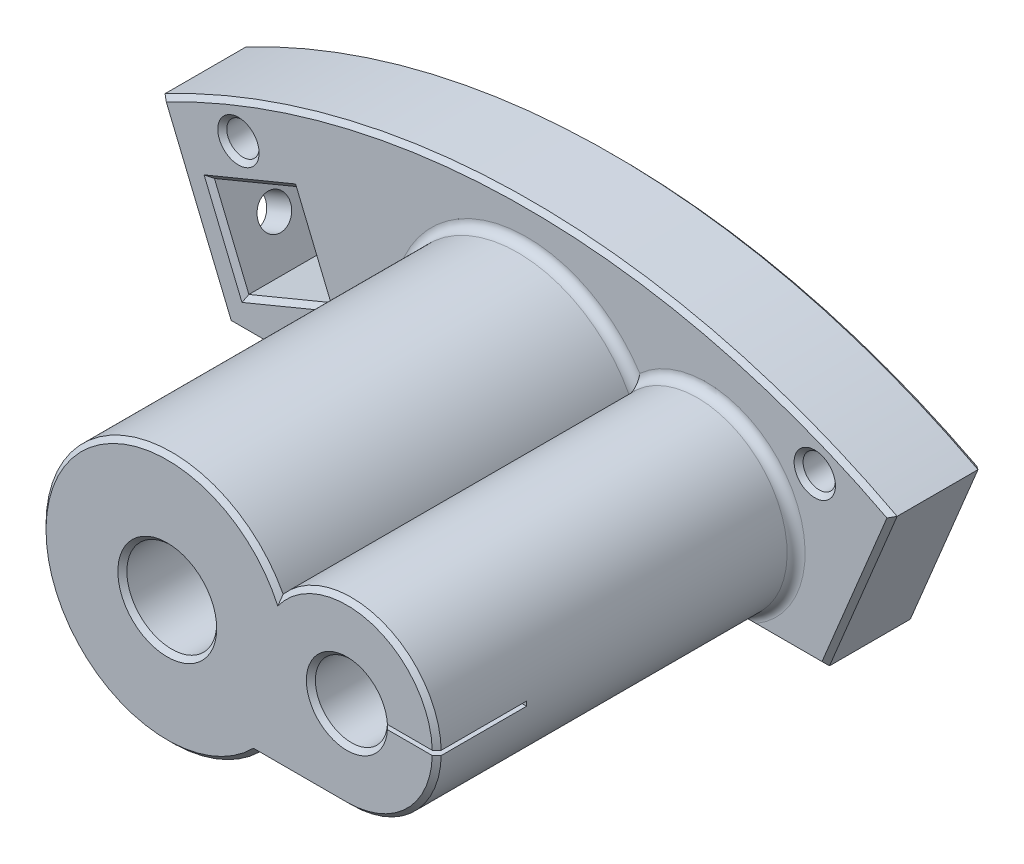
SolidWorks part; units mm, degrees
ref_plane "Front Plane" through (0, 0, 0) normal (0, 0, 1) x (1, 0, 0)
ref_plane "Top Plane" through (0, 0, 0) normal (0, 1, 0) x (1, 0, 0)
ref_plane "Right Plane" through (0, 0, 0) normal (1, 0, 0) x (0, 0, -1)
sketch "Sketch1" plane through (0, 0, 0) normal (0, 0, 1) x (1, 0, 0)
  line L0 (-46.9014, 0) -> (43.5211, 0) construction
  line L1 (0, 38.5211) -> (0, -80.4339) construction
  line L2 (-33.5349, -69.25) -> (36.7559, -69.25) construction
  line L3 (0, -69.25) -> (-37.9703, 22.4183) construction
  line L4 (-40.7467, 8.1836) -> (-33.2148, -10)
  line L5 (-25.9885, 6.5901) -> (-35.2504, 2.7537)
  line L6 (-35.2504, 2.7537) -> (-31.414, -6.5082)
  line L7 (-31.414, -6.5082) -> (-22.1521, -2.6718)
  line L8 (-22.1521, -2.6718) -> (-25.9885, 6.5901)
  line L9 (-33.2148, -10) -> (-9.798, -10)
  line L10 (33.2148, -10) -> (9.798, -10)
  line L11 (40.7467, 8.1836) -> (33.2148, -10)
  line L12 (20, 7.6656) -> (20, -13.8845) construction
  circle A1 centre (-28.7013, 0.041) radius 5.0125 construction
  arc A2 (40.7467, 8.1836) -> (-40.7467, 8.1836) centre (0, -69.25) ccw
  arc A5 (-9.798, -10) -> (9.798, -10) centre (0, 0) ccw
  circle A6 centre (0, 0) radius 5
  circle A7 centre (-32.0765, 8.1894) radius 1.8
  circle A8 centre (32.0765, 8.1894) radius 1.8
  circle A9 centre (20, 0) radius 3
  point P32 (0, -14)
  dimension "D2" = 20
  dimension "D7" = 75
  dimension "D8" = 175
  dimension "D9" = 3
  dimension "D10" = 14
  dimension "D12" = 10
  dimension "D13" = 3.6
  dimension "D14" = 32.0765
  dimension "D16" = 6
  dimension "D3" = 69.25
  dimension "D4" = 22.5
  dimension "D5" = 10.025
  dimension "D6" = 90
  dimension "D11" = 10
extrude "Boss-Extrude1" add sketch "Sketch1" along normal blind 10
sketch "Sketch3" plane through (0, 0, 0) normal (0, 0, -1) x (-1, 0, 0)
  circle A0 centre (0, 0) radius 11.025
  dimension "D1" = 22.05
sketch "Sketch4" plane through (0, 0, 0) normal (0, 0, -1) x (-1, 0, 0)
  circle A0 centre (0, 0) radius 12.525
  dimension "D1" = 25.05
sketch "Sketch5" plane through (-29.1145, -12.0596, 0) normal (0.9239, 0.3827, 0) x (0, 0, -1)
  line L5 (-10, 16.0338) -> (0, 16.0338) construction
  line L6 (0, 16.0338) -> (0, 6.0088) construction
  circle A0 centre (-4.75, 11.0188) radius 1.8
  dimension "D1" = 3.6
  dimension "D2" = 5.015
  dimension "D3" = 4.75
extrude "Cut-Extrude4" cut sketch "Sketch5" against normal blind 10
sketch "Sketch6" plane through (0, 0, 10) normal (0, 0, 1) x (1, 0, 0)
  line L1 (9.798, -10) -> (20, -10)
  line L2 (0, 22.1581) -> (0, -16.2187) construction
  arc A2 (12.4, 6.4992) -> (9.798, -10) centre (0, 0) ccw
  arc A3 (20, -10) -> (12.4, 6.4992) centre (20, 0) ccw
  circle A4 centre (0, 0) radius 5 construction
  circle A5 centre (0, 0) radius 5
  circle A6 centre (20, 0) radius 3 construction
  circle A7 centre (20, 0) radius 3
  dimension "D1" = 28
  dimension "D2" = 20
  dimension "D3" = 20
extrude "Boss-Extrude3" add sketch "Sketch6" along normal blind 40
sketch "Sketch7" plane through (0, 0, 50) normal (0, 0, 1) x (1, 0, 0)
  circle A0 centre (0, 0) radius 11.025
  dimension "D1" = 22.05
sketch "Sketch8" plane through (0, 0, 50) normal (0, 0, 1) x (1, 0, 0)
  circle A0 centre (0, 0) radius 12.525
  dimension "D1" = 25.05
sketch "Sketch9" plane through (0, 0, 50) normal (0, 0, 1) x (1, 0, 0)
  line L0 (-15.573, 0) -> (48.0602, 0) construction
  line L1 (24.0047, 0.25) -> (29.9969, 0.25)
  line L2 (24.0047, -0.25) -> (29.9969, -0.25)
  arc A0 (24.0047, 0.25) -> (24.0047, -0.25) centre (20, 0) ccw
  arc A1 (20, -10) -> (12.4, 6.4992) centre (20, 0) ccw construction
  arc A2 (29.9969, -0.25) -> (29.9969, 0.25) centre (20, 0) ccw
  dimension "D1" = 8.025
  dimension "D2" = 0.25
extrude "Cut-Extrude7" cut sketch "Sketch9" against normal blind 10
chamfer "Chamfer1" distance 0.5 17 edges at (30.2765, 8.1894, 10) (-33.3322, -1.8772, 10) (-26.7831, -4.59, 10) (-24.0703, 1.9592, 10) (-30.6195, 4.6719, 10) (-30.2765, 8.1894, 10) (26.6074, -10, 10) (36.9808, -0.9082, 10) (0, 18.25, 10) (-21.5064, -10, 10) (-36.9808, -0.9082, 10) (15.9875, 0, 50) (26.9821, -7.1589, 50) (14.899, -10, 50) (23.3466, 9.4234, 50) (-13.8291, 2.1809, 50) (5, 0, 50)
fillet "Fillet1" radius 1 2 edges at (28.307, 5.5672, 10) (-8.0693, 11.4406, 10)
sketch "Sketch10" plane through (0, 0, 0) normal (0, 0, -1) x (-1, 0, 0)
  circle A2 centre (-20, 0) radius 3 construction
  circle A3 centre (-20, 0) radius 3
extrude "Boss-Extrude4" add sketch "Sketch10" against normal blind 40
chamfer "Chamfer2" distance 0.5 angle 45 13 edges at (30.2765, 8.1894, 0) (-30.2765, 8.1894, 0) (-26.7831, -4.59, 0) (-33.3322, -1.8772, 0) (-30.6195, 4.6719, 0) (-24.0703, 1.9592, 0) (0, 18.25, 0) (-36.9808, -0.9082, 0) (-21.5064, -10, 0) (0, -14, 0) (21.5064, -10, 0) (36.9808, -0.9082, 0) (5, 0, 0)
